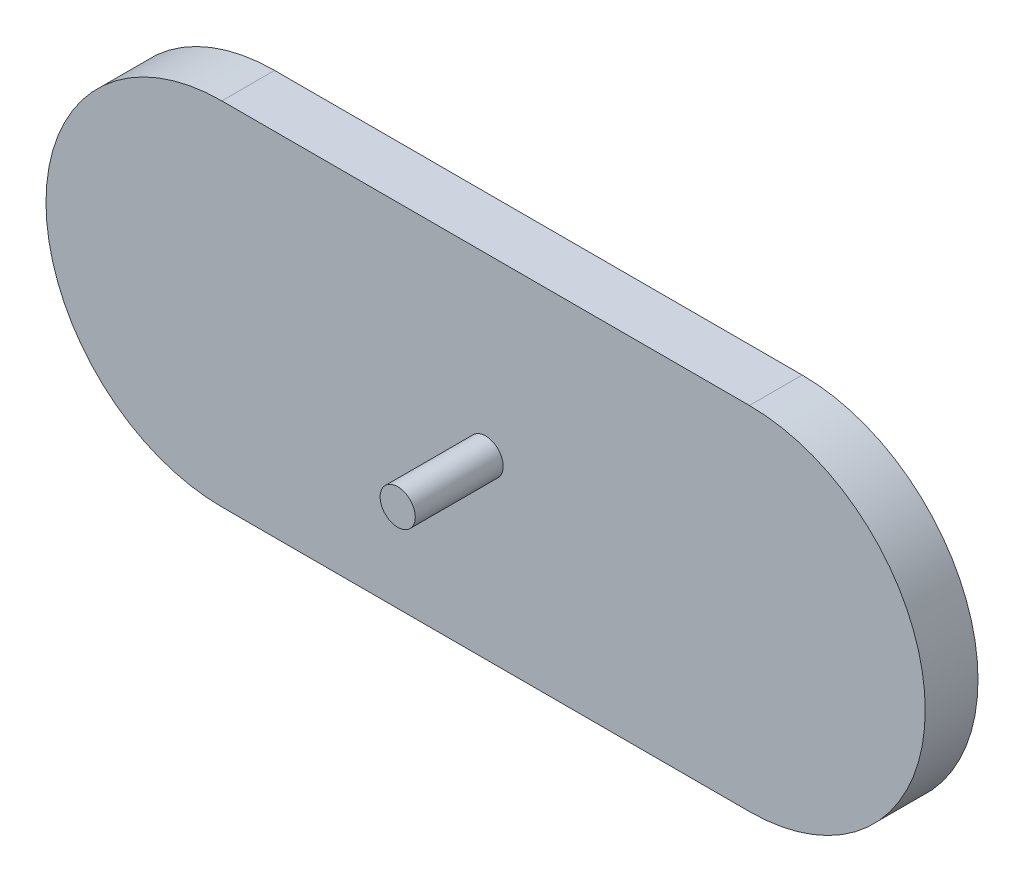
SolidWorks part; units mm, degrees
ref_plane "前视基准面" through (0, 0, 0) normal (0, 0, 1) x (1, 0, 0)
ref_plane "上视基准面" through (0, 0, 0) normal (0, 1, 0) x (1, 0, 0)
ref_plane "右视基准面" through (0, 0, 0) normal (1, 0, 0) x (0, 0, -1)
sketch "草图1" plane through (0, 0, 0) normal (0, 0, 1) x (1, 0, 0)
  line L0 (0, 50) -> (-150, 50)
  line L5 (0, 0) -> (-150, 0)
  line L6 (0, 0) -> (0, 100)
  line L7 (0, 100) -> (-150, 100)
  line L8 (-150, 0) -> (-150, 100)
  circle A6 centre (0, 50) radius 50
  circle A7 centre (0, 50) radius 25
  circle A8 centre (-150, 50) radius 50
  circle A9 centre (-150, 50) radius 25
  circle A10 centre (-75, 50) radius 5
  dimension "D1" = 100
  dimension "D2" = 150
  dimension "D3" = 50
  dimension "D4" = 50
  dimension "D5" = 10
extrude "凸台-拉伸1" add sketch "草图1" along normal blind 15 contours L7 L8 L5 L6
extrude "凸台-拉伸4" add sketch "草图1<10>" along normal blind 15 contours A7 L6 A6 | L6 A7 | L8 A9 | A9 L8 A8 region at (-151.118, 87.5, 0) region at (-160.6103, 50, 0) region at (34.5648, 84.5648, 0) region at (10.6103, 50, 0)
sketch "草图1<10>" plane through (0, 0, 0) normal (0, 0, 1) x (1, 0, 0) same geometry as "草图1"
extrude "凸台-拉伸5" add sketch "草图1<13>" along normal blind 40 contours L0 A10 | L0 A10 region at (-75, 52.1221, 0) region at (-75, 47.8779, 0)
sketch "草图1<13>" plane through (0, 0, 0) normal (0, 0, 1) x (1, 0, 0) same geometry as "草图1"
